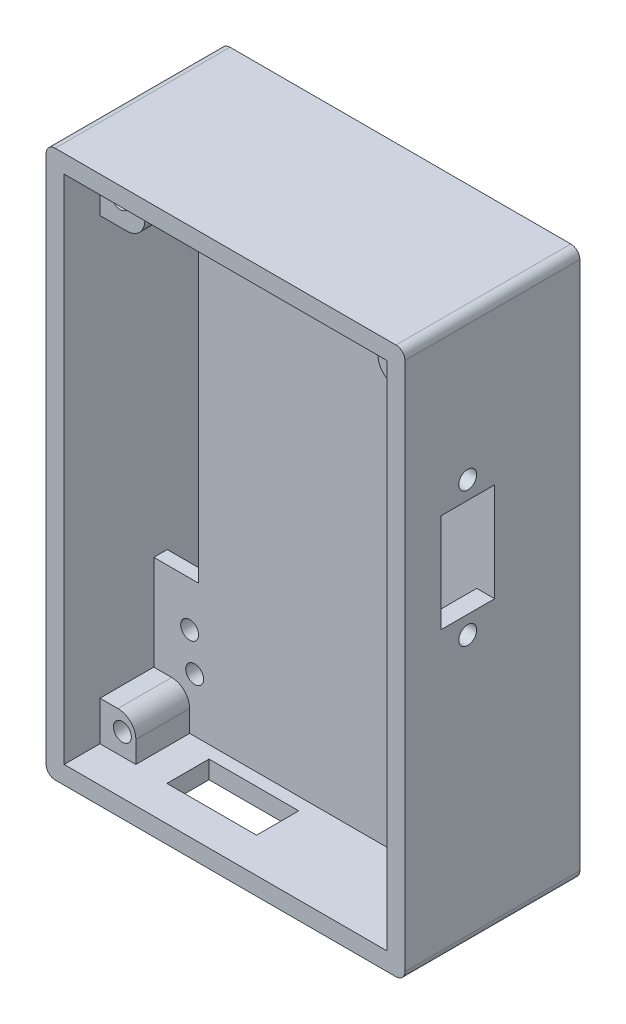
SolidWorks part; units mm, degrees
other "标注1"
sketch "草图16" plane through (38, 59, 11) normal (0.1952, 0.5523, 0.8105) x (0.9731, -0.0061, -0.2302)
other "标注2"
sketch "草图17" plane through (38, 59, 11) normal (0.1952, 0.5523, 0.8105) x (0.9731, -0.0061, -0.2302)
ref_plane "前视基准面" through (0, 0, 0) normal (0, 0, 1) x (1, 0, 0)
ref_plane "上视基准面" through (0, 0, 0) normal (0, 1, 0) x (1, 0, 0)
ref_plane "右视基准面" through (0, 0, 0) normal (1, 0, 0) x (0, 0, -1)
other "Configuration Table"
sketch "草图1" plane through (0, 0, 0) normal (0, 0, 1) x (1, 0, 0)
  line L1 (0, 0) -> (36, 0)
  line L2 (0, 0) -> (0, 57)
  line L3 (0, 57) -> (36, 57)
  line L4 (36, 0) -> (36, 57)
  line L5 (0, 15) -> (5, 15)
  line L6 (0, 15) -> (0, 51)
  line L7 (0, 51) -> (5, 51)
  line L8 (5, 15) -> (5, 51)
  line L9 (-2, 59) -> (-2, -2) construction
  line L10 (28.75, 16) -> (30.25, 16)
  line L11 (38, -2) -> (-2, -2) construction
  line L12 (28.75, 16) -> (28.75, 52)
  line L13 (38, -2) -> (38, 59) construction
  line L15 (38, 59) -> (-2, 59) construction
  line L16 (30.25, 16) -> (30.25, 52)
  line L17 (-1, -2) -> (37, -2)
  line L18 (-2, -1) -> (-2, 58)
  line L19 (-1, 59) -> (37, 59)
  line L20 (38, -1) -> (38, 58)
  line L21 (7.25, 52) -> (28.75, 52)
  line L23 (5.75, 53.5) -> (30.25, 53.5)
  line L24 (30.25, 52) -> (30.25, 53.5)
  line L25 (5.75, 46) -> (7.25, 46)
  line L26 (5.75, 46) -> (5.75, 53.5)
  line L28 (7.25, 46) -> (7.25, 52)
  line L29 (5.75, 16) -> (7.25, 16)
  line L30 (5.75, 16) -> (5.75, 25)
  line L31 (5.75, 25) -> (7.25, 25)
  line L32 (7.25, 16) -> (7.25, 25)
  circle A2 centre (4.56, 6) radius 1
  circle A3 centre (30.56, 6) radius 1
  circle A4 centre (4, 10) radius 1
  circle A5 centre (31, 10) radius 1
  arc A6 (37, -2) -> (38, -1) centre (37, -1) ccw
  arc A7 (-1, -2) -> (-2, -1) centre (-1, -1) cw
  arc A8 (38, 58) -> (37, 59) centre (37, 58) ccw
  arc A9 (-2, 58) -> (-1, 59) centre (-1, 58) cw
  point P20 (-2, -2)
  point P27 (38, -2)
  point P30 (-2, -2)
  point P33 (38, 59)
  dimension "D7" = 4
  dimension "D11" = 1
  dimension "D1" = 36
  dimension "D2" = 57
  dimension "D3" = 2
  dimension "D4" = 2
  dimension "D5" = 2
  dimension "D6" = 2
  dimension "D8" = 5
  dimension "D9" = 4.56
  dimension "D10" = 5.44
  dimension "D12" = 36
  dimension "D13" = 5
  dimension "D14" = 37.5
  dimension "D15" = 1.5
  dimension "D16" = 24.5
  dimension "D17" = 6
  dimension "D19" = 1.5
  dimension "D20" = 21.5
  dimension "D21" = 9
  dimension "D22" = 1.5
  dimension "D23" = 16
sketch "草图2" plane through (0, 0, 0) normal (0, 0, 1) x (1, 0, 0)
  line L7 (0, 0) -> (4, 0)
  line L8 (0, 0) -> (0, 4.4)
  line L9 (0, 4.4) -> (2, 4.4)
  line L10 (0, 0) -> (36, 0) construction
  line L13 (4, 0) -> (4, 2.4)
  line L14 (36, 0) -> (32, 0)
  line L15 (36, 0) -> (36, 4.4)
  line L16 (36, 4.4) -> (34, 4.4)
  line L17 (32, 0) -> (32, 2.4)
  line L18 (36, 57) -> (31, 57)
  line L19 (36, 57) -> (36, 51)
  line L20 (36, 51) -> (33, 51)
  line L21 (31, 57) -> (31, 53)
  line L22 (0, 57) -> (5, 57)
  line L23 (0, 57) -> (0, 51)
  line L24 (0, 51) -> (3, 51)
  line L25 (5, 57) -> (5, 53)
  circle A0 centre (2.5, 2.4) radius 1
  circle A1 centre (34, 2.4) radius 1
  circle A2 centre (2.25, 53.6994) radius 1
  circle A3 centre (33.75, 53.6994) radius 1
  arc A9 (4, 2.4) -> (2, 4.4) centre (2, 2.4) ccw
  arc A10 (34, 4.4) -> (32, 2.4) centre (34, 2.4) ccw
  arc A11 (33, 51) -> (31, 53) centre (33, 53) cw
  arc A12 (3, 51) -> (5, 53) centre (3, 53) ccw
  point P16 (2.0001, 0)
  point P18 (2, 4.3)
  point P25 (3.9, 2.4)
  point P28 (1.9999, 4.2999)
  dimension "D1" = 2
  dimension "D10" = 2
  dimension "D11" = 2
  dimension "D12" = 2
  dimension "D13" = 2
  dimension "D14" = 2
  dimension "D15" = 2
  dimension "D3" = 2.4
  dimension "D4" = 2.4
  dimension "D5" = 31.5
  dimension "D6" = 51.3
  dimension "D7" = 31.5
  dimension "D16" = 5
  dimension "D17" = 6
  dimension "D18" = 6
  dimension "D19" = 5
  dimension "D20" = 4
  dimension "D21" = 4.4
  dimension "D22" = 4.4
  dimension "D23" = 4
  dimension "D24" = 51.3
extrude "螺丝柱" add sketch "草图2" along normal blind 7.5
sketch "ESP32开口" plane through (0, 0, 0) normal (0, 1, 0) x (1, 0, 0)
  line L1 (12.56, 0) -> (22.56, 0)
  line L2 (12.56, 0) -> (12.56, 4.7)
  line L3 (12.56, 4.7) -> (22.56, 4.7)
  line L4 (22.56, 0) -> (22.56, 4.7)
  line L5 (38, 0) -> (-2, 0) construction
  dimension "D1" = 4.7
  dimension "D2" = 10
  dimension "D3" = 0
sketch "草图15" plane through (0, 0, 0) normal (0, -1, 0) x (1, 0, 0)
  line L1 (7.56, 2.9) -> (17.56, 2.9)
  line L2 (7.56, 2.9) -> (7.56, 7.6)
  line L3 (7.56, 7.6) -> (17.56, 7.6)
  line L4 (17.56, 2.9) -> (17.56, 7.6)
extrude "反向螺柱" add sketch "草图2<5>" against normal blind 4.5
sketch "草图2<5>" plane through (0, 0, 0) normal (0, 0, 1) x (1, 0, 0) same geometry as "草图2"
extrude "电源管理板外壳" add sketch "草图1" along normal blind 11.5 contours L17 L20 L19 L18 L4 L1 L2 L3 region at (-1.1913, -1.1913, 0)
extrude "电源管理板开口" cut sketch "草图15" along normal up to surface (2 mm away) up to face at (18, -2, 5.75)
extrude "ESP32外壳" add sketch "草图1" against normal blind 8 contours L17 L20 L19 L18 L4 L1 L2 L3 region at (-1.1913, -1.1913, 0)
extrude "ESP32" cut sketch "ESP32开口" against normal up to surface (2 mm away) up to face at (18, -2, 1.75)
extrude "底板" add sketch "草图1<29>" along normal blind 1.5 contours L8 L5 L2 L1 L4 L3 L7 A5 A4 A3 A2 L32 L29 L30 L31 L28 L25 L26 L23 L24 L16 L10 L12 L21 region at (19.3937, 27.4594, 0)
sketch "草图1<29>" plane through (0, 0, 0) normal (0, 0, 1) x (1, 0, 0) same geometry as "草图1"
extrude "凸台-拉伸3" add sketch "草图1<30>" against normal blind 2.5 separate body contours L25 L28 L21 L12 L10 L16 L24 L23 L26 | L29 L32 L31 L30 region at (29.1979, 34, 0) region at (6.5, 20.5, 0)
sketch "草图1<30>" plane through (0, 0, 0) normal (0, 0, 1) x (1, 0, 0) same geometry as "草图1"
extrude "凸台-拉伸4" add sketch "草图1<31>" along normal blind 1.5 contours L30 L31 L32 L29 | L12 L21 L28 L25 L26 L23 L24 L16 L10
sketch "草图1<31>" plane through (0, 0, 0) normal (0, 0, 1) x (1, 0, 0) same geometry as "草图1"
sketch "草图18" plane through (38, 0, 0) normal (1, 0, 0) x (0, 0, -1)
  line L1 (-7.5, 30) -> (-1.5, 30)
  line L2 (-7.5, 30) -> (-7.5, 41)
  line L3 (-7.5, 41) -> (-1.5, 41)
  line L4 (-1.5, 30) -> (-1.5, 41)
  circle A0 centre (-4.5, 43) radius 1
  circle A1 centre (-4.5, 28) radius 1
  dimension "D1" = 11
  dimension "D2" = 6
extrude "开关" cut sketch "草图18" against normal up to surface (2 mm away) up to face at (36, 28.1, 7)
